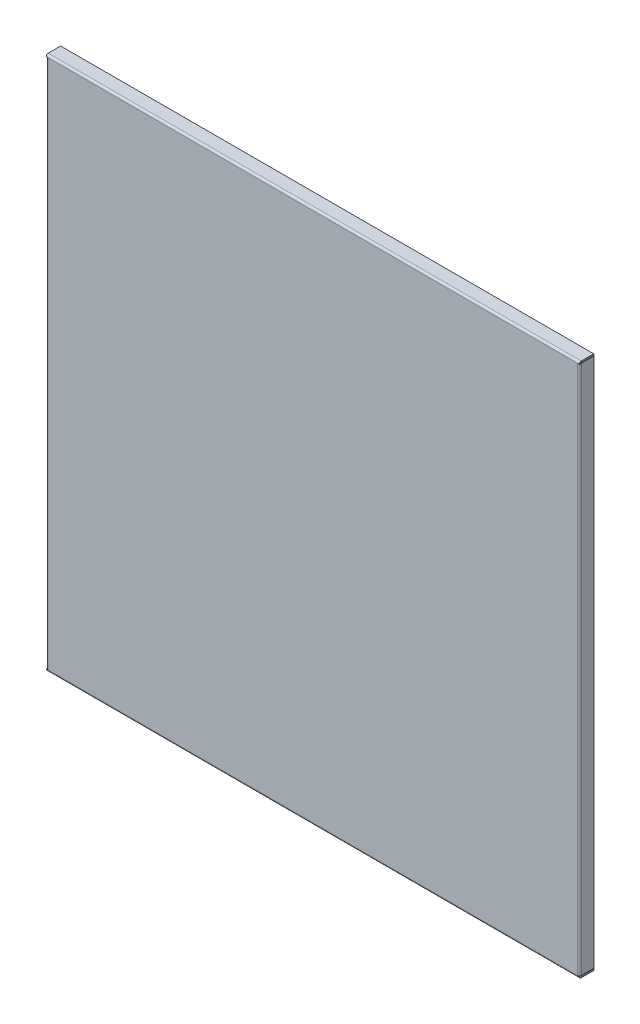
SolidWorks part; units mm, degrees
note: The reader was unsure of these and kept them because the rebuilt part matched: flange length of "边线-法兰2", "边线-法兰3".
ref_plane "前视基准面" through (0, 0, 0) normal (0, 0, 1) x (1, 0, 0)
ref_plane "上视基准面" through (0, 0, 0) normal (0, 1, 0) x (1, 0, 0)
ref_plane "右视基准面" through (0, 0, 0) normal (1, 0, 0) x (0, 0, -1)
sketch "草图2" plane through (0, 0, 0) normal (0, 0, 1) x (1, 0, 0)
  line L0 (-277.5, -278) -> (-277.5, 278)
  line L1 (-277.5, -278) -> (277.5, -278)
  line L2 (-277.5, 278) -> (277.5, 278)
  line L3 (277.5, -278) -> (277.5, 278)
  line L4 (-277.5, -278) -> (277.5, 278) construction
  line L5 (-277.5, 278) -> (277.5, -278) construction
  point P1 (0, 0)
  dimension "D1" = 555
  dimension "D2" = 556
base flange "基体-法兰1" sketch "草图2" thickness 1.5 reverse thickness direction no parameters "D1"=0.5
edge flange "边线-法兰2" sketch "草图25" flange profiles "草图25", "草图26" flange angle 90 flange length 15 flange position material inside bend radius 0.5 thickness 1.5 relief obround parameters "D6"=10, "D8"=0.5
sketch "草图25" plane through (0, 278, -1.5) normal (0, 1, 0) x (1, 0, 0)
  line L0 (277.5, 0) -> (-277.5, 0) construction
  line L1 (277.5, 0) -> (-277.5, 0)
  line L2 (-277.5, 0) -> (-277.5, 13.5)
  line L3 (-277.5, 13.5) -> (277.5, 13.5)
  line L4 (277.5, 13.5) -> (277.5, 0)
sketch "草图26" plane through (0, -278, -1.5) normal (0, -1, 0) x (-1, 0, 0)
  line L0 (277.5, 0) -> (-277.5, 0) construction
  line L1 (277.5, 0) -> (-277.5, 0)
  line L2 (-277.5, 0) -> (-277.5, 13.5)
  line L3 (-277.5, 13.5) -> (277.5, 13.5)
  line L4 (277.5, 13.5) -> (277.5, 0)
bend "边线折弯5" bend radius 0.5 bend angle 90 parameters "D5"=1
bend "边线折弯6" bend radius 0.5 bend angle 90 parameters "D5"=2
edge flange "边线-法兰3" sketch "草图33" flange profiles "草图33", "草图34" flange angle 90 flange length 15 flange position material inside bend radius 0.5 thickness 1.5 relief none parameters "D6"=10, "D8"=0.5
sketch "草图33" plane through (-277.5, 0, -1.5) normal (-1, 0, 0) x (0, 1, 0)
  line L0 (276, 0) -> (-276, 0) construction
  line L1 (276, 0) -> (-276, 0)
  line L2 (-276, 0) -> (-276, 13.5)
  line L3 (-276, 13.5) -> (276, 13.5)
  line L4 (276, 13.5) -> (276, 0)
sketch "草图34" plane through (277.5, 0, -1.5) normal (1, 0, 0) x (0, -1, 0)
  line L0 (276, 0) -> (-276, 0) construction
  line L1 (276, 0) -> (-276, 0)
  line L2 (-276, 0) -> (-276, 13.5)
  line L3 (-276, 13.5) -> (276, 13.5)
  line L4 (276, 13.5) -> (276, 0)
bend "边线折弯7" bend radius 0.5 bend angle 90 parameters "D5"=3
bend "边线折弯8" bend radius 0.5 bend angle 90 parameters "D5"=4
sketch "折弯-线1" [suppressed] plane through (0, 0, 0) normal (0, 1, 0) x (1, 0, 0)
sketch "边界框1" [suppressed] plane through (0, 0, 0) normal (0, 1, 0) x (1, 0, 0)
sheet metal parameters "钣金6" thickness 1.5 parameters "D1"=0.5
flat pattern "平板型式6" [suppressed]
sketch "折弯-线2" plane through (0, 0, 0) normal (0, 1, 0) x (1, 0, 0)
sketch "边界框2" [suppressed] plane through (0, 0, 0) normal (0, 1, 0) x (1, 0, 0)
sheet metal parameters "钣金8" thickness 1.5 parameters "D1"=0.5
flat pattern "平板型式6" [suppressed]
sketch "折弯-线2" plane through (0, 0, 0) normal (0, 1, 0) x (1, 0, 0)
sketch "边界框2" [suppressed] plane through (0, 0, 0) normal (0, 1, 0) x (1, 0, 0)
bend of the flat pattern "展开-<边线折弯5>1"
bend of the flat pattern "展开-<边线折弯6>1"
sheet metal parameters "钣金9" thickness 1.5 parameters "D1"=0.5
flat pattern "平板型式6"
sketch "折弯-线2" plane through (0, 0, 0) normal (0, 0, 1) x (1, 0, 0)
  line L0 (276.3, -276) -> (276.3, 276) construction
  line L1 (-276.3, 276) -> (-276.3, -276) construction
  line L2 (-277.5, -276.8) -> (277.5, -276.8) construction
  line L3 (277.5, 276.8) -> (-277.5, 276.8) construction
  line L4 (276.3, -276) -> (276.3, 276) construction
  line L5 (-276.3, 276) -> (-276.3, -276) construction
  line L6 (-277.5, -276.8) -> (277.5, -276.8) construction
  line L7 (277.5, 276.8) -> (-277.5, 276.8) construction
sketch3d "边界框2" [suppressed]
  line L0 (290.1, 290.6, 0) -> (290.1, -290.6, 0) construction
  line L1 (-290.1, 290.6, 0) -> (-290.1, -290.6, 0) construction
  line L2 (290.1, 290.6, 0) -> (-290.1, 290.6, 0) construction
  line L3 (290.1, -290.6, 0) -> (-290.1, -290.6, 0) construction
bend of the flat pattern "展开-<边线折弯5>1"
bend of the flat pattern "展开-<边线折弯6>1"
bend of the flat pattern "展开-<边线折弯7>1"
bend of the flat pattern "展开-<边线折弯8>1"
